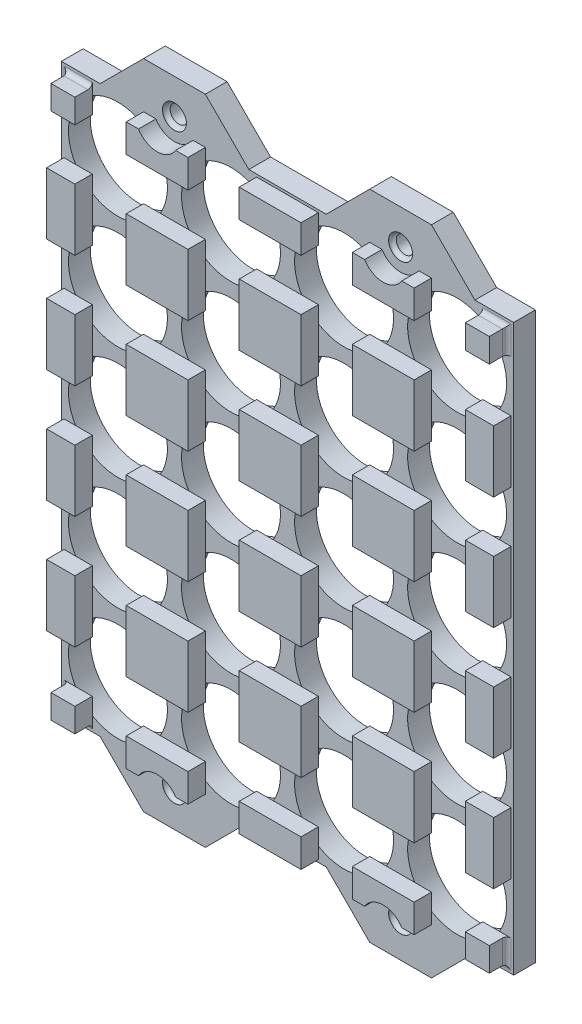
SolidWorks part; units mm, degrees
ref_plane "Front Plane" through (0, 0, 0) normal (0, 0, 1) x (1, 0, 0)
ref_plane "Top Plane" through (0, 0, 0) normal (0, 1, 0) x (1, 0, 0)
ref_plane "Right Plane" through (0, 0, 0) normal (1, 0, 0) x (0, 0, -1)
sketch "Szkic1" plane through (0, 0, 0) normal (0, 0, 1) x (1, 0, 0)
  line L1 (-20.2054, 8.0552) -> (83.7946, 8.0552)
  line L2 (-20.2054, 8.0552) -> (-20.2054, -17.9448)
  line L3 (-20.2054, -17.9448) -> (83.7946, -17.9448)
  line L4 (83.7946, 8.0552) -> (83.7946, -17.9448)
  circle A0 centre (-7.2054, -4.9448) radius 8.854
  circle A1 centre (-7.2054, -4.9448) radius 11.3761
  circle A2 centre (18.7946, -4.9448) radius 8.854
  circle A3 centre (18.7946, -4.9448) radius 11.3761
  circle A4 centre (44.7946, -4.9448) radius 8.854
  circle A5 centre (44.7946, -4.9448) radius 11.3761
  circle A6 centre (70.7946, -4.9448) radius 8.854
  circle A7 centre (70.7946, -4.9448) radius 11.3761
  circle A10 centre (96.7946, -4.9448) radius 8.854 [skipped]
  circle A11 centre (96.7946, -4.9448) radius 11.3761 [skipped]
  dimension "D2" = 13
  dimension "D5" = 13
  dimension "D1" = 5
extrude "Dodanie-wyciągnięcie1" add sketch "Szkic1" along normal blind 5 contours L4 L1 L2 L3 A7 A5 A3 A1 region at (31.7946, -4.9448, 0)
sketch "Szkic15" plane through (0, 0, 0) normal (0, 0, 1) x (1, 0, 0)
  line L6 (-20.2054, -4.9448) -> (-32.3088, -4.9448)
  line L41 (-18.6054, 6.4552) -> (-13.1054, 6.4552)
  line L42 (-18.6054, 6.4552) -> (-18.6054, 0.9552)
  line L43 (-18.6054, 0.9552) -> (-13.1054, 0.9552)
  line L44 (-13.1054, 6.4552) -> (-13.1054, 0.9552)
  line L45 (4.1946, 0.9552) -> (-1.3054, 0.9552)
  line L46 (4.1946, 6.4552) -> (4.1946, 0.9552)
  line L47 (4.1946, 6.4552) -> (-1.3054, 6.4552)
  line L48 (-1.3054, 6.4552) -> (-1.3054, 0.9552)
  line L49 (7.3946, 0.9552) -> (12.8946, 0.9552)
  line L50 (12.8946, 6.4552) -> (12.8946, 0.9552)
  line L51 (7.3946, 6.4552) -> (12.8946, 6.4552)
  line L52 (7.3946, 6.4552) -> (7.3946, 0.9552)
  line L53 (30.1946, 6.4552) -> (24.6946, 6.4552)
  line L54 (24.6946, 6.4552) -> (24.6946, 0.9552)
  line L55 (30.1946, 6.4552) -> (30.1946, 0.9552)
  line L56 (30.1946, 0.9552) -> (24.6946, 0.9552)
  line L57 (33.3946, 0.9552) -> (38.8946, 0.9552)
  line L58 (38.8946, 6.4552) -> (38.8946, 0.9552)
  line L59 (33.3946, 6.4552) -> (38.8946, 6.4552)
  line L60 (33.3946, 6.4552) -> (33.3946, 0.9552)
  line L61 (56.1946, 6.4552) -> (50.6946, 6.4552)
  line L62 (50.6946, 6.4552) -> (50.6946, 0.9552)
  line L63 (56.1946, 6.4552) -> (56.1946, 0.9552)
  line L64 (56.1946, 0.9552) -> (50.6946, 0.9552)
  line L65 (59.3946, 0.9552) -> (64.8946, 0.9552)
  line L66 (64.8946, 6.4552) -> (64.8946, 0.9552)
  line L67 (59.3946, 6.4552) -> (64.8946, 6.4552)
  line L68 (59.3946, 6.4552) -> (59.3946, 0.9552)
  line L69 (82.1946, 6.4552) -> (76.6946, 6.4552)
  line L70 (76.6946, 6.4552) -> (76.6946, 0.9552)
  line L71 (82.1946, 6.4552) -> (82.1946, 0.9552)
  line L72 (82.1946, 0.9552) -> (76.6946, 0.9552)
  line L105 (56.1946, -7.5448) -> (50.6946, -7.5448) [skipped]
  line L106 (56.1946, -7.5448) -> (56.1946, -13.0448) [skipped]
  line L107 (56.1946, -13.0448) -> (50.6946, -13.0448) [skipped]
  line L108 (59.3946, -13.0448) -> (64.8946, -13.0448) [skipped]
  line L109 (64.8946, -7.5448) -> (64.8946, -13.0448) [skipped]
  line L110 (59.3946, -7.5448) -> (64.8946, -7.5448) [skipped]
  line L111 (59.3946, -7.5448) -> (59.3946, -13.0448) [skipped]
  line L112 (82.1946, -7.5448) -> (76.6946, -7.5448) [skipped]
  line L113 (76.6946, -7.5448) -> (76.6946, -13.0448) [skipped]
  line L114 (82.1946, -7.5448) -> (82.1946, -13.0448) [skipped]
  line L115 (82.1946, -13.0448) -> (76.6946, -13.0448) [skipped]
  line L116 (7.3946, -13.0448) -> (12.8946, -13.0448) [skipped]
  line L117 (12.8946, -7.5448) -> (12.8946, -13.0448) [skipped]
  line L118 (7.3946, -7.5448) -> (12.8946, -7.5448) [skipped]
  line L119 (7.3946, -7.5448) -> (7.3946, -13.0448) [skipped]
  line L120 (30.1946, -7.5448) -> (24.6946, -7.5448) [skipped]
  line L121 (24.6946, -7.5448) -> (24.6946, -13.0448) [skipped]
  line L122 (30.1946, -7.5448) -> (30.1946, -13.0448) [skipped]
  line L123 (30.1946, -13.0448) -> (24.6946, -13.0448) [skipped]
  line L124 (33.3946, -13.0448) -> (38.8946, -13.0448) [skipped]
  line L125 (38.8946, -7.5448) -> (38.8946, -13.0448) [skipped]
  line L126 (33.3946, -7.5448) -> (38.8946, -7.5448) [skipped]
  line L127 (33.3946, -7.5448) -> (33.3946, -13.0448) [skipped]
  line L128 (50.6946, -7.5448) -> (50.6946, -13.0448) [skipped]
  line L129 (-18.6054, -13.0448) -> (-13.1054, -13.0448) [skipped]
  line L130 (-13.1054, -7.5448) -> (-13.1054, -13.0448) [skipped]
  line L131 (-18.6054, -7.5448) -> (-13.1054, -7.5448) [skipped]
  line L132 (-18.6054, -7.5448) -> (-18.6054, -13.0448) [skipped]
  line L133 (4.1946, -7.5448) -> (-1.3054, -7.5448) [skipped]
  line L134 (-1.3054, -7.5448) -> (-1.3054, -13.0448) [skipped]
  line L135 (4.1946, -7.5448) -> (4.1946, -13.0448) [skipped]
  line L136 (4.1946, -13.0448) -> (-1.3054, -13.0448) [skipped]
  line L138 (82.1946, -10.8448) -> (76.6946, -10.8448)
  line L139 (82.1946, -16.3448) -> (82.1946, -10.8448)
  line L140 (76.6946, -16.3448) -> (76.6946, -10.8448)
  line L141 (82.1946, -16.3448) -> (76.6946, -16.3448)
  line L142 (59.3946, -16.3448) -> (59.3946, -10.8448)
  line L143 (59.3946, -16.3448) -> (64.8946, -16.3448)
  line L144 (64.8946, -16.3448) -> (64.8946, -10.8448)
  line L145 (59.3946, -10.8448) -> (64.8946, -10.8448)
  line L146 (56.1946, -10.8448) -> (50.6946, -10.8448)
  line L147 (56.1946, -16.3448) -> (56.1946, -10.8448)
  line L148 (50.6946, -16.3448) -> (50.6946, -10.8448)
  line L149 (56.1946, -16.3448) -> (50.6946, -16.3448)
  line L150 (33.3946, -16.3448) -> (33.3946, -10.8448)
  line L151 (33.3946, -16.3448) -> (38.8946, -16.3448)
  line L152 (38.8946, -16.3448) -> (38.8946, -10.8448)
  line L153 (33.3946, -10.8448) -> (38.8946, -10.8448)
  line L154 (30.1946, -10.8448) -> (24.6946, -10.8448)
  line L155 (30.1946, -16.3448) -> (30.1946, -10.8448)
  line L156 (24.6946, -16.3448) -> (24.6946, -10.8448)
  line L157 (30.1946, -16.3448) -> (24.6946, -16.3448)
  line L158 (7.3946, -16.3448) -> (7.3946, -10.8448)
  line L159 (7.3946, -16.3448) -> (12.8946, -16.3448)
  line L160 (12.8946, -16.3448) -> (12.8946, -10.8448)
  line L161 (7.3946, -10.8448) -> (12.8946, -10.8448)
  line L162 (-1.3054, -16.3448) -> (-1.3054, -10.8448)
  line L163 (4.1946, -16.3448) -> (-1.3054, -16.3448)
  line L164 (4.1946, -16.3448) -> (4.1946, -10.8448)
  line L165 (4.1946, -10.8448) -> (-1.3054, -10.8448)
  line L166 (-13.1054, -16.3448) -> (-13.1054, -10.8448)
  line L167 (-18.6054, -10.8448) -> (-13.1054, -10.8448)
  line L168 (-18.6054, -16.3448) -> (-18.6054, -10.8448)
  line L169 (-18.6054, -16.3448) -> (-13.1054, -16.3448)
  point P5 (-18.6054, 6.4552)
  point P71 (-18.6054, -16.3448)
  dimension "D1" = 5.5
extrude "Dodanie-wyciągnięcie7" add sketch "Szkic15" along normal blind 4 from surface contours L167 L166 L169 L168 | L41 L44 L43 L42 | L47 L48 L45 L46 | L51 L50 L49 L52 | L165 L162 L163 L164 | L161 L160 L159 L158 | L53 L54 L56 L55 | L59 L58 L57 L60 | L153 L152 L151 L150 | L154 L156 L157 L155 | L61 L62 L64 L63 | L67 L66 L65 L68 | L145 L144 L143 L142 | L146 L148 L149 L147 | L69 L70 L72 L71 | L138 L140 L141 L139 starting at face at (82.1707, -4.9448, 5)
fillet "Zaokrąglenie9" radius 1 32 edges at (82.1946, 3.7052, 5) (79.4446, 6.4552, 5) (82.1946, -13.5948, 5) (79.4446, -16.3448, 5) (59.3946, 3.7052, 5) (62.1446, 6.4552, 5) (59.3946, -13.5948, 5) (62.1446, -16.3448, 5) (53.4446, -16.3448, 5) (56.1946, -13.5948, 5) (56.1946, 3.7052, 5) (53.4446, 6.4552, 5) (36.1446, 6.4552, 5) (33.3946, 3.7052, 5) (33.3946, -13.5948, 5) (36.1446, -16.3448, 5) (27.4446, -16.3448, 5) (30.1946, -13.5948, 5) (30.1946, 3.7052, 5) (27.4446, 6.4552, 5) (-18.6054, -13.5948, 5) (-15.8554, -16.3448, 5) (10.1446, -16.3448, 5) (1.4446, -16.3448, 5) (4.1946, -13.5948, 5) (7.3946, -13.5948, 5) (7.3946, 3.7052, 5) (10.1446, 6.4552, 5) (4.1946, 3.7052, 5) (1.4446, 6.4552, 5) (-15.8554, 6.4552, 5) (-18.6054, 3.7052, 5)
pattern_linear "Szyk liniowy9" count 5 spacing 26 along (0, 1, 0) of "Dodanie-wyciągnięcie1", "Dodanie-wyciągnięcie7", "Zaokrąglenie9"
sketch "Szkic16" plane through (0, 0, 5) normal (0, 0, 1) x (1, 0, 0)
  line L1 (-1.3054, 93.1552) -> (12.8946, 93.1552)
  line L2 (-1.3054, 93.1552) -> (-1.3054, 78.9552)
  line L3 (-1.3054, 78.9552) -> (12.8946, 78.9552)
  line L4 (12.8946, 93.1552) -> (12.8946, 78.9552)
  line L5 (24.6946, 93.1552) -> (38.8946, 93.1552)
  line L6 (24.6946, 93.1552) -> (24.6946, 78.9552)
  line L7 (24.6946, 78.9552) -> (38.8946, 78.9552)
  line L8 (38.8946, 93.1552) -> (38.8946, 78.9552)
  line L9 (50.6946, 93.1552) -> (64.8946, 93.1552)
  line L10 (50.6946, 93.1552) -> (50.6946, 78.9552)
  line L11 (50.6946, 78.9552) -> (64.8946, 78.9552)
  line L12 (64.8946, 93.1552) -> (64.8946, 78.9552)
  line L13 (-1.3054, 67.1552) -> (12.8946, 67.1552)
  line L14 (-1.3054, 67.1552) -> (-1.3054, 52.9552)
  line L15 (-1.3054, 52.9552) -> (12.8946, 52.9552)
  line L16 (12.8946, 67.1552) -> (12.8946, 52.9552)
  line L17 (24.6946, 67.1552) -> (38.8946, 67.1552)
  line L18 (24.6946, 67.1552) -> (24.6946, 52.9552)
  line L19 (24.6946, 52.9552) -> (38.8946, 52.9552)
  line L20 (38.8946, 67.1552) -> (38.8946, 52.9552)
  line L21 (50.6946, 67.1552) -> (64.8946, 67.1552)
  line L22 (50.6946, 67.1552) -> (50.6946, 52.9552)
  line L23 (50.6946, 52.9552) -> (64.8946, 52.9552)
  line L24 (64.8946, 67.1552) -> (64.8946, 52.9552)
  line L25 (50.6946, 41.1552) -> (64.8946, 41.1552)
  line L26 (50.6946, 41.1552) -> (50.6946, 26.9552)
  line L27 (50.6946, 26.9552) -> (64.8946, 26.9552)
  line L28 (64.8946, 41.1552) -> (64.8946, 26.9552)
  line L29 (24.6946, 41.1552) -> (38.8946, 41.1552)
  line L30 (24.6946, 41.1552) -> (24.6946, 26.9552)
  line L31 (24.6946, 26.9552) -> (38.8946, 26.9552)
  line L32 (38.8946, 41.1552) -> (38.8946, 26.9552)
  line L33 (-1.3054, 41.1552) -> (12.8946, 41.1552)
  line L34 (-1.3054, 41.1552) -> (-1.3054, 26.9552)
  line L35 (-1.3054, 26.9552) -> (12.8946, 26.9552)
  line L36 (12.8946, 41.1552) -> (12.8946, 26.9552)
  line L37 (-1.3054, 15.1552) -> (12.8946, 15.1552)
  line L38 (-1.3054, 15.1552) -> (-1.3054, 0.9552)
  line L39 (-1.3054, 0.9552) -> (12.8946, 0.9552)
  line L40 (12.8946, 15.1552) -> (12.8946, 0.9552)
  line L41 (24.6946, 15.1552) -> (38.8946, 15.1552)
  line L42 (24.6946, 15.1552) -> (24.6946, 0.9552)
  line L43 (24.6946, 0.9552) -> (38.8946, 0.9552)
  line L44 (38.8946, 15.1552) -> (38.8946, 0.9552)
  line L45 (50.6946, 15.1552) -> (64.8946, 15.1552)
  line L46 (50.6946, 15.1552) -> (50.6946, 0.9552)
  line L47 (50.6946, 0.9552) -> (64.8946, 0.9552)
  line L48 (64.8946, 15.1552) -> (64.8946, 0.9552)
  line L49 (-1.3054, 111.4552) -> (12.8946, 111.4552)
  line L50 (-1.3054, 111.4552) -> (-1.3054, 104.9552)
  line L51 (-1.3054, 104.9552) -> (12.8946, 104.9552)
  line L52 (12.8946, 111.4552) -> (12.8946, 104.9552)
  line L53 (24.6946, 111.4552) -> (38.8946, 111.4552)
  line L54 (24.6946, 111.4552) -> (24.6946, 104.9552)
  line L55 (24.6946, 104.9552) -> (38.8946, 104.9552)
  line L56 (38.8946, 111.4552) -> (38.8946, 104.9552)
  line L57 (50.6946, 111.4552) -> (64.8946, 111.4552)
  line L58 (50.6946, 111.4552) -> (50.6946, 104.9552)
  line L59 (50.6946, 104.9552) -> (64.8946, 104.9552)
  line L60 (64.8946, 111.4552) -> (64.8946, 104.9552)
  line L61 (76.6946, 93.1552) -> (83.1946, 93.1552)
  line L62 (76.6946, 93.1552) -> (76.6946, 78.9552)
  line L63 (76.6946, 78.9552) -> (83.1946, 78.9552)
  line L64 (83.1946, 93.1552) -> (83.1946, 78.9552)
  line L65 (76.6946, 67.1552) -> (83.1946, 67.1552)
  line L66 (76.6946, 67.1552) -> (76.6946, 52.9552)
  line L67 (76.6946, 52.9552) -> (83.1946, 52.9552)
  line L68 (83.1946, 67.1552) -> (83.1946, 52.9552)
  line L69 (76.6946, 41.1552) -> (83.1946, 41.1552)
  line L70 (76.6946, 41.1552) -> (76.6946, 26.9552)
  line L71 (76.6946, 26.9552) -> (83.1946, 26.9552)
  line L72 (83.1946, 41.1552) -> (83.1946, 26.9552)
  line L73 (76.6946, 15.1552) -> (83.1946, 15.1552)
  line L74 (76.6946, 15.1552) -> (76.6946, 0.9552)
  line L75 (76.6946, 0.9552) -> (83.1946, 0.9552)
  line L76 (83.1946, 15.1552) -> (83.1946, 0.9552)
  line L77 (50.6946, -10.8448) -> (64.8946, -10.8448)
  line L78 (50.6946, -10.8448) -> (50.6946, -17.3448)
  line L79 (50.6946, -17.3448) -> (64.8946, -17.3448)
  line L80 (64.8946, -10.8448) -> (64.8946, -17.3448)
  line L81 (24.6946, -10.8448) -> (38.8946, -10.8448)
  line L82 (24.6946, -10.8448) -> (24.6946, -17.3448)
  line L83 (24.6946, -17.3448) -> (38.8946, -17.3448)
  line L84 (38.8946, -10.8448) -> (38.8946, -17.3448)
  line L85 (-1.3054, -10.8448) -> (12.8946, -10.8448)
  line L86 (-1.3054, -10.8448) -> (-1.3054, -17.3448)
  line L87 (-1.3054, -17.3448) -> (12.8946, -17.3448)
  line L88 (12.8946, -10.8448) -> (12.8946, -17.3448)
  line L89 (-19.6054, 15.1552) -> (-13.1054, 15.1552)
  line L90 (-19.6054, 15.1552) -> (-19.6054, 0.9552)
  line L91 (-19.6054, 0.9552) -> (-13.1054, 0.9552)
  line L92 (-13.1054, 15.1552) -> (-13.1054, 0.9552)
  line L93 (-19.6054, 41.1552) -> (-13.1054, 41.1552)
  line L94 (-19.6054, 41.1552) -> (-19.6054, 26.9552)
  line L95 (-19.6054, 26.9552) -> (-13.1054, 26.9552)
  line L96 (-13.1054, 41.1552) -> (-13.1054, 26.9552)
  line L97 (-19.6054, 67.1552) -> (-13.1054, 67.1552)
  line L98 (-19.6054, 67.1552) -> (-19.6054, 52.9552)
  line L99 (-19.6054, 52.9552) -> (-13.1054, 52.9552)
  line L100 (-13.1054, 67.1552) -> (-13.1054, 52.9552)
  line L101 (-19.6054, 93.1552) -> (-13.1054, 93.1552)
  line L102 (-19.6054, 93.1552) -> (-19.6054, 78.9552)
  line L103 (-19.6054, 78.9552) -> (-13.1054, 78.9552)
  line L104 (-13.1054, 93.1552) -> (-13.1054, 78.9552)
extrude "Dodanie-wyciągnięcie8" add sketch "Szkic16" along normal blind 4
sketch "Szkic17" plane through (0, 112.0552, 0) normal (0, 1, 0) x (1, 0, 0)
  line L0 (-20.2054, 0) -> (83.7946, 0) construction
  line L1 (-1.3054, -5) -> (12.8946, -5)
  line L2 (-1.3054, -5) -> (-1.3054, 0)
  line L3 (-1.3054, 0) -> (12.8946, 0)
  line L4 (12.8946, -5) -> (12.8946, 0)
  line L5 (50.6946, -9) -> (50.6946, -5) construction
  line L6 (50.6946, 0) -> (64.8946, 0)
  line L7 (50.6946, 0) -> (50.6946, -5)
  line L8 (50.6946, -5) -> (64.8946, -5)
  line L9 (64.8946, 0) -> (64.8946, -5)
  dimension "D1" = 0
extrude "Dodanie-wyciągnięcie9" add sketch "Szkic17" along normal blind 10
ref_plane "Płaszczyzna4" through (0, 47.0552, 0) normal (0, 1, 0) x (1, 0, 0)
sketch "Szkic19" plane through (0, 0, 0) normal (0, 0, -1) x (-1, 0, 0)
  line L0 (-57.7946, 122.0552) -> (-57.7946, 106.6429)
  line L1 (-64.8946, 122.0552) -> (-50.6946, 122.0552) construction
  line L2 (-31.7946, 112.0552) -> (-31.7946, 127.0552)
  line L3 (-12.8946, 112.0552) -> (-50.6946, 112.0552) construction
  circle A0 centre (-57.7946, 114.0552) radius 2
  circle A1 centre (-57.7946, 114.0552) radius 5
  circle A2 centre (-70.7946, 99.0552) radius 11.3761 construction
  circle A3 centre (-5.7946, 114.0552) radius 2
  circle A4 centre (-5.7946, 114.0552) radius 5
  dimension "D1" = 4
  dimension "D2" = 3
  dimension "D3" = 15
extrude "Wytnij-wyciągnięcie1" cut sketch "Szkic19" against normal blind 10 contours A3 | A0
extrude "Wytnij-wyciągnięcie2" cut sketch "Szkic19<4>" against normal blind 10 from surface contours A1 | A4 starting at face at (18.7946, 8.0552, 5)
sketch "Szkic19<4>" plane through (0, 0, 0) normal (0, 0, -1) x (-1, 0, 0) same geometry as "Szkic19"
mirror "Lustro1" about plane through (0, 47.0552, 0) normal (0, 1, 0) of "Wytnij-wyciągnięcie2", "Dodanie-wyciągnięcie9", "Wytnij-wyciągnięcie1"
chamfer "Sfazowanie2" distance 10 angle 45 8 edges at (12.8946, 112.0552, 2.5) (64.8946, -17.9448, 2.5) (12.8946, -17.9448, 2.5) (50.6946, -17.9448, 2.5) (-1.3054, -17.9448, 2.5) (64.8946, 112.0552, 2.5) (50.6946, 112.0552, 2.5) (-1.3054, 112.0552, 2.5)
sketch "Szkic20" plane through (0, 0, 5) normal (0, 0, 1) x (1, 0, 0)
  line L0 (-20.2054, 47.0552) -> (83.7946, 47.0552)
  line L1 (-20.2054, 112.0552) -> (-20.2054, -17.9448) construction
  line L2 (83.7946, 112.0552) -> (83.7946, -17.9448) construction
  line L3 (83.7946, 47.0552) -> (31.7946, 47.0552)
  line L4 (31.7946, 47.0552) -> (31.7946, 137.5565)
  circle A0 centre (5.7946, 114.0552) radius 2.75
  circle A1 centre (57.7946, 114.0552) radius 2.75
  circle A2 centre (57.7946, -19.9448) radius 2.75
  circle A3 centre (5.7946, -19.9448) radius 2.75
  dimension "D1" = 5.5
extrude "Wytnij-wyciągnięcie3" cut sketch "Szkic20" against normal blind 1 contours A0 | A1 | A3 | A2 region at (5.7946, 114.0552, 5) region at (57.7946, 114.0552, 5)
fillet "Zaokrąglenie10" radius 1 4 edges at (60.5446, -19.9448, 4) (3.0446, -19.9448, 4) (60.5446, 114.0552, 4) (8.5446, 114.0552, 4)
